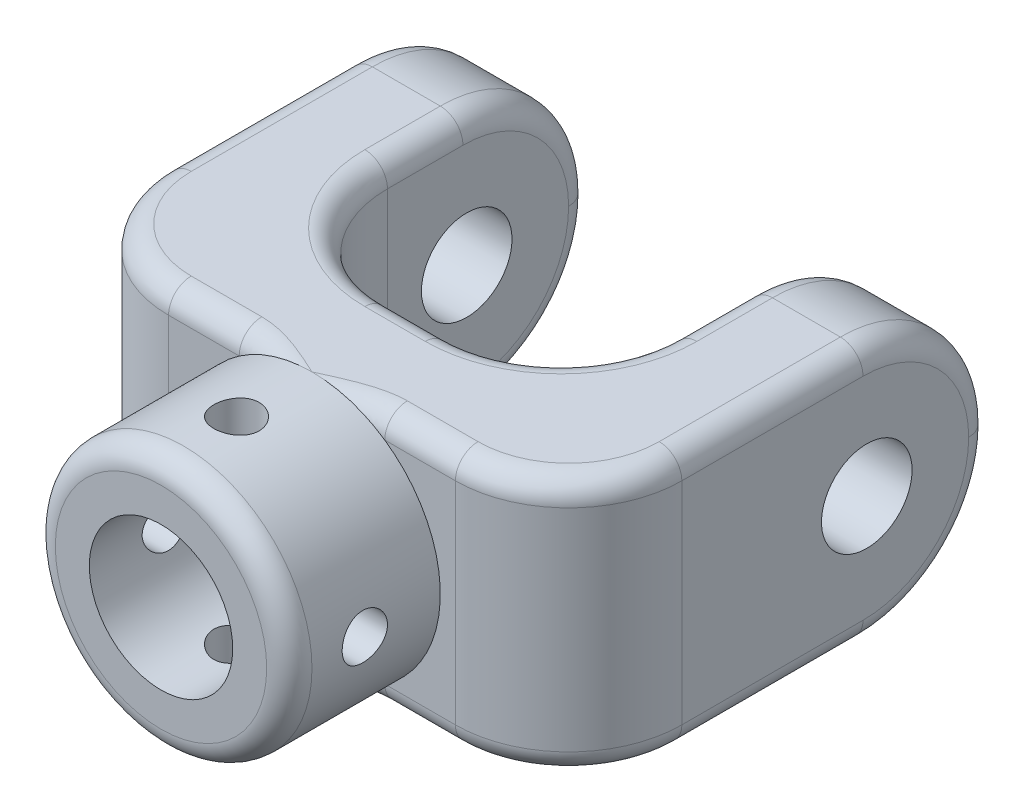
SolidWorks part; units mm, degrees
ref_plane "Front Plane" through (0, 0, 0) normal (0, 0, 1) x (1, 0, 0)
ref_plane "Top Plane" through (0, 0, 0) normal (0, 1, 0) x (1, 0, 0)
ref_plane "Right Plane" through (0, 0, 0) normal (1, 0, 0) x (0, 0, -1)
sketch "Sketch1" plane through (0, 0, 0) normal (0, 1, 0) x (1, 0, 0)
  line L0 (-34, 0) -> (34, 0)
  line L1 (34, 0) -> (34, 56)
  line L2 (34, 56) -> (19, 56)
  line L3 (19, 56) -> (19, 14)
  line L4 (19, 14) -> (-19, 14)
  line L5 (0, 14) -> (0, 0) construction
  line L6 (-34, 0) -> (-34, 56)
  line L7 (-34, 56) -> (-19, 56)
  line L8 (-19, 56) -> (-19, 14)
  dimension "D1" = 34
  dimension "D2" = 14
  dimension "D3" = 56
  dimension "D4" = 15
  dimension "D5" = 19
extrude "Boss-Extrude2" add sketch "Sketch1" along normal mid plane 34
fillet "Fillet2" radius 17 4 edges at (-26.5, -17, -56) (-26.5, 17, -56) (26.5, -17, -56) (26.5, 17, -56)
sketch "Sketch4" plane through (0, 0, 0) normal (0, 0, 1) x (1, 0, 0)
  circle A0 centre (0, 0) radius 17
  dimension "D1" = 34
extrude "Boss-Extrude3" add sketch "Sketch4" along normal blind 20
fillet "Fillet3" radius 3 1 edges at (17, 0, 20)
fillet "Fillet4" radius 15 4 edges at (19, 0, -14) (-19, 0, -14) (34, 0, 0) (-34, 0, 0)
fillet "Fillet5" radius 3 30 edges at (19, 12.0208, -51.0208) (19, -12.0208, -51.0208) (19, -17, -34) (14.6066, -17, -18.3934) (0, -17, -14) (-14.6066, -17, -18.3934) (-19, -17, -34) (-19, -12.0208, -51.0208) (-19, 12.0208, -51.0208) (-34, 12.0208, -51.0208) (-34, -12.0208, -51.0208) (-34, -17, -27) (-29.6066, -17, -4.3934) (-9.5, -17, 0) (9.5, -17, 0) (29.6066, -17, -4.3934) (34, -17, -27) (34, -12.0208, -51.0208) (34, 12.0208, -51.0208) (-9.5, 17, 0) (-29.6066, 17, -4.3934) (-34, 17, -27) (-19, 17, -34) (-14.6066, 17, -18.3934) (0, 17, -14) (14.6066, 17, -18.3934) (19, 17, -34) (34, 17, -27) (29.6066, 17, -4.3934) (9.5, 17, 0)
sketch "Sketch5" plane through (0, 0, 20) normal (0, 0, 1) x (1, 0, 0)
  circle A0 centre (0, 0) radius 9.5
  dimension "D1" = 19
extrude "Cut-Extrude1" cut sketch "Sketch5" against normal through all
sketch "Sketch6" plane through (34, 0, 0) normal (1, 0, 0) x (0, 0, -1)
  circle A0 centre (39.5, 0) radius 6
  point P2 (45.5, 0)
  point P4 (0, 0)
  dimension "D1" = 12
  dimension "D2" = 10.5
extrude "Cut-Extrude2" cut sketch "Sketch6" against normal through all
sketch "Sketch7" plane through (0, 0, 0) normal (0, 1, 0) x (1, 0, 0)
  line L0 (-14, -20) -> (14, -20) construction
  circle A0 centre (0, -10) radius 3
  point P5 (0, 0)
  dimension "D1" = 6
  dimension "D2" = 10
extrude "Cut-Extrude3" cut sketch "Sketch7" against normal through all
pattern_circular "CirPattern1" count 4 over 360 about axis through (0, 0, 20) along (0, 0, -1) of "Cut-Extrude3"
